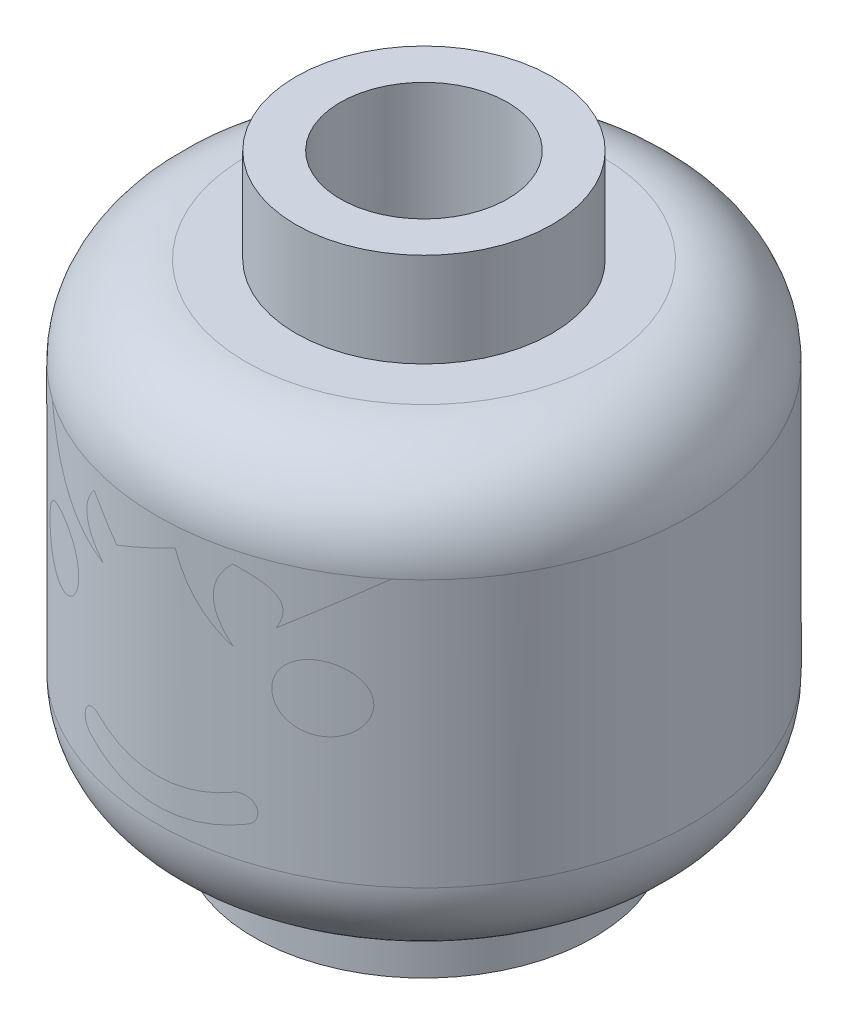
SolidWorks part; units mm, degrees
ref_plane "Front Plane" through (0, 0, 0) normal (0, 0, 1) x (1, 0, 0)
ref_plane "Top Plane" through (0, 0, 0) normal (0, 1, 0) x (1, 0, 0)
ref_plane "Right Plane" through (0, 0, 0) normal (1, 0, 0) x (0, 0, -1)
sketch "Sketch1" plane through (0, 0, 0) normal (0, 0, 1) x (1, 0, 0)
  line L0 (0, 0) -> (0, 11.4) construction
  line L1 (0, 9.4) -> (1.6, 9.4)
  line L2 (1.6, 9.4) -> (1.6, 11.4)
  line L3 (1.6, 11.4) -> (2.45, 11.4)
  line L4 (2.45, 11.4) -> (2.45, 9.6)
  line L5 (2.45, 9.6) -> (3.4, 9.6)
  line L6 (5.1, 7.9) -> (5.1, 2.8)
  line L7 (3.4, 1.1) -> (3.25, 1.1)
  line L8 (3.25, 1.1) -> (3.25, 0)
  line L9 (3.25, 0) -> (2.45, 0)
  line L10 (2.45, 0) -> (2.45, 8.5)
  line L11 (2.45, 8.5) -> (0, 8.5)
  line L12 (0, 8.5) -> (0, 9.4)
  arc A0 (5.1, 2.8) -> (3.4, 1.1) centre (3.4, 2.8) cw
  arc A1 (3.4, 9.6) -> (5.1, 7.9) centre (3.4, 7.9) cw
  dimension "D10" = 1.7
  dimension "D1" = 1.6
  dimension "D2" = 2
  dimension "D3" = 1.8
  dimension "D4" = 2.9
  dimension "D5" = 2.45
  dimension "D6" = 2.65
  dimension "D7" = 0.8
  dimension "D8" = 1.1
  dimension "D9" = 9.6
  dimension "D11" = 2.45
revolve "Revolve1" add sketch "Sketch1" angle 360 about L0
sketch "Sketch2" plane through (0, 0, 0) normal (0, 0, 1) x (1, 0, 0)
  line L0 (0, 11.4) -> (0, 0) construction
  line L1 (2.45, 11.4) -> (-2.45, 11.4) construction
  line L2 (-5.1, 5.8) -> (5.098, 5.8) construction
  line L3 (-5.1, 7.9) -> (-5.1, 2.8) construction
  line L4 (-5.1, 3.1) -> (5.1, 3.1) construction
  line L5 (5.1, 2.8) -> (5.1, 7.9) construction
  line L6 (1.6, 11.4) -> (-1.6, 11.4) construction
  line L7 (-3.25, 0) -> (3.25, 0) construction
  line L8 (5.1, 7.9) -> (-5.1, 7.9) construction
  line L9 (-1.4, 7.5309) -> (-0.8439, 6.9626)
  line L10 (-0.8439, 6.9626) -> (0.3331, 7.5309)
  line L11 (1.9025, 6.8171) -> (3.2817, 7.9)
  line L12 (3.2817, 7.9) -> (-2.9319, 7.9)
  circle A0 centre (-2.47, 5.8) radius 0.625
  circle A1 centre (2.47, 5.8) radius 0.625
  arc A2 (1.4, 3.667) -> (-1.4, 3.667) centre (0, 6.6) cw construction
  arc A3 (-1.5077, 3.4414) -> (1.5077, 3.4414) centre (0, 6.6) ccw
  arc A4 (-1.2923, 3.8926) -> (1.2923, 3.8926) centre (0, 6.6) ccw
  arc A5 (-1.2923, 3.8926) -> (-1.5077, 3.4414) centre (-1.4, 3.667) ccw
  arc A6 (1.5077, 3.4414) -> (1.2923, 3.8926) centre (1.4, 3.667) ccw
  spline S0 degree 2 poles (-2.9319, 7.9) (-2.3811, 6.7328) (-1.1715, 6.4748) knots 0 0 0 1 1 1
  spline S1 degree 2 poles (-1.1715, 6.4748) (-1.8983, 6.958) (-1.4, 7.5309) knots 0 0 0 1 1 1
  spline S2 degree 2 poles (0.3331, 7.5309) (0.5973, 6.7218) (1.2923, 6.2997) knots 0 0 0 1 1 1
  spline S3 degree 2 poles (1.2923, 6.2997) (0.6703, 7.0706) (1.2801, 7.6662) knots 0 0 0 1 1 1
  spline S4 degree 2 poles (1.2801, 7.6662) (2.2583, 7.4484) (1.9025, 6.8171) knots 0 0 0 1 1 1
  point P24 (0, 3.35)
  dimension "D3" = 1.25
  dimension "D5" = 0.25
  dimension "D7" = 3.5
  dimension "D1" = 5.6
  dimension "D2" = 3.1
  dimension "D4" = 4.94
  dimension "D6" = 2.8
split line "Split Line1"
sketch "Sketch3" plane through (0, 9.4, 0) normal (0, 1, 0) x (1, 0, 0)
  line L0 (0, 0) -> (0, 1.6) construction
  line L1 (0, 0) -> (-1.3856, -0.8) construction
  line L2 (-0.42, 0.2425) -> (-1.547, -0.4082)
  line L3 (-0.42, 0.2425) -> (-0.42, 1.5439)
  line L4 (-0.42, 0.2425) -> (-0.42, 1.6) construction
  line L5 (-0.42, 0.2425) -> (-1.5956, -0.4363) construction
  circle A0 centre (0, 0) radius 1.6 construction
  circle A2 centre (0, 0) radius 1.6
  arc A3 (-0.42, 1.5439) -> (-1.547, -0.4082) centre (0, 0) ccw
  dimension "D1" = 120
  dimension "D2" = 0.42
  dimension "D3" = 0
extrude "Cut-Extrude1" cut sketch "Sketch3" against normal through all
pattern_circular "CirPattern1" count 3 over 360 about axis through (0, 0, 0) along (0, -1, 0) of "Cut-Extrude1" reverse direction yes
